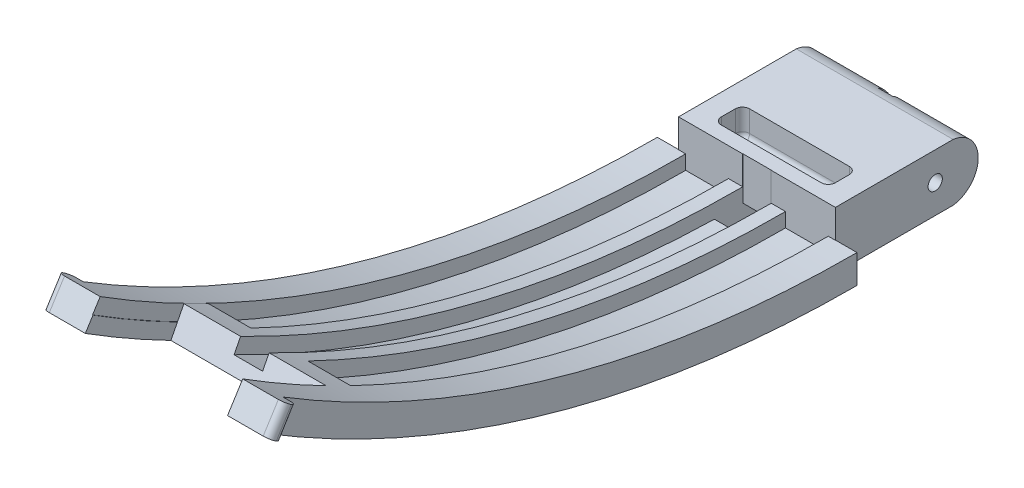
SolidWorks part; units mm, degrees
ref_plane "Alzado" through (0, 0, 0) normal (0, 0, 1) x (1, 0, 0)
ref_plane "Planta" through (0, 0, 0) normal (0, 1, 0) x (1, 0, 0)
ref_plane "Vista lateral" through (0, 0, 0) normal (1, 0, 0) x (0, 0, -1)
sketch "Croquis1" plane through (0, 0, 0) normal (0, 1, 0) x (1, 0, 0)
  line L1 (39.1869, -12.1528) -> (50.1869, -12.1528)
  line L2 (39.1869, -12.1528) -> (39.1869, -22.1528)
  line L3 (39.1869, -22.1528) -> (50.1869, -22.1528)
  line L4 (50.1869, -12.1528) -> (50.1869, -22.1528)
  dimension "D1" = 10
  dimension "D2" = 11
extrude "Saliente-Extruir1" add sketch "Croquis1" along normal blind 4
sketch "Croquis2" plane through (39.1869, 0, 0) normal (-1, 0, 0) x (0, 0, 1)
  line L0 (12.1528, 0) -> (12.1528, 2)
  line L1 (12.1528, 4) -> (12.1528, 0) construction
  line L2 (12.1528, 2) -> (22.1528, 2)
  line L3 (22.1528, 4) -> (22.1528, 0) construction
  line L4 (12.1528, 2) -> (19.1486, 2)
  line L5 (22.1528, 2) -> (15.1528, 2)
  line L6 (12.1528, 2) -> (15.1528, 2)
  circle A0 centre (15.1528, 2) radius 0.5
  dimension "D2" = 1
  dimension "D1" = 7
  dimension "D3" = 3
extrude "Cortar-Extruir1" cut sketch "Croquis2" against normal blind 12 contours A0
sketch "Croquis3" plane through (0, 4, 0) normal (0, 1, 0) x (1, 0, 0)
  line L0 (39.1869, -22.1528) -> (50.1869, -22.1528)
  line L1 (39.1869, -22.1528) -> (50.1869, -22.1528) construction
  line L2 (39.1869, -12.1528) -> (39.1869, -22.1528) construction
  line L3 (40.6869, -19.1753) -> (48.6869, -19.1753)
  line L4 (40.6869, -19.1753) -> (40.6869, -21.1528)
  line L5 (40.6869, -21.1528) -> (48.6869, -21.1528)
  line L6 (48.6869, -19.1753) -> (48.6869, -21.1528)
  line L7 (50.1869, -22.1528) -> (50.1869, -12.1528) construction
  dimension "D1" = 1
  dimension "D2" = 1.5
  dimension "D3" = 1.5
extrude "Cortar-Extruir2" cut sketch "Croquis3" against normal blind 2 contours L6 L3 L4 L5 region at (44.6869, 4, 20.1641)
fillet "Redondeo6" radius 0.5 4 edges at (48.6869, 3, 19.1753) (48.6869, 3, 21.1528) (40.6869, 3, 21.1528) (40.6869, 3, 19.1753)
fillet "Redondeo8" radius 0.5 8 edges at (48.5405, 2, 19.3218) (44.6869, 2, 19.1753) (40.8334, 2, 19.3218) (40.6869, 2, 20.1641) (40.8334, 2, 21.0064) (44.6869, 2, 21.1528) (48.5405, 2, 21.0064) (48.6869, 2, 20.1641)
sketch "Croquis4" plane through (50.1869, 0, 0) normal (1, 0, 0) x (0, 0, -1)
  line L0 (-22.1528, 4) -> (-22.1528, 0)
  line L1 (-12.1528, 2) -> (-14.1528, 2)
  line L2 (-12.1528, 4) -> (-12.1528, 0) construction
  line L3 (-12.1528, 2) -> (-12.1528, 4)
  line L4 (-12.1528, 0) -> (-12.1528, 2)
  line L5 (-12.1528, 4) -> (-14.1528, 4.0162)
  circle A0 centre (-14.1528, 2) radius 2.0162
  spline S0 degree 1 poles (-14.1528, -0.0162) (-12.1528, 0) knots 0 0 1 1
  line M2 (-22.1528, 0) -> (-12.1528, 0)
  line M3 (-12.1528, 0) -> (-12.1528, 4)
  line M4 (-12.1528, 4) -> (-22.1528, 4)
  dimension "D1" = 2
extrude "Cortar-Extruir3" cut sketch "Croquis4" against normal blind 20 contours A0 L3 M4 | A0 M2 M3 region at (50.1869, 3.5672, 12.5857) region at (50.1869, 0.4328, 12.5857)
sketch "Croquis5" plane through (0, 0, 0) normal (0, -1, 0) x (1, 0, 0)
  line L0 (44.6869, 17.97) -> (44.6869, 12.1528)
  line L1 (39.1869, 12.1528) -> (50.1869, 12.1528) construction
  line L2 (44.6869, 12.1528) -> (44.6869, 17.97)
  line L3 (44.6869, 17.97) -> (44.6869, 22.1528)
  line L4 (39.1869, 22.1528) -> (50.1869, 22.1528) construction
  line L5 (44.6869, 22.1528) -> (44.6869, 20.1528)
  line L6 (39.1869, 13.8975) -> (39.1869, 22.1528) construction
  line L7 (44.6869, 20.1528) -> (45.1869, 20.1528)
  line L8 (44.6869, 20.1528) -> (44.6869, 12.1528)
  line L9 (44.6869, 12.1528) -> (45.1869, 12.1528)
  line L10 (45.1869, 20.1528) -> (45.1869, 12.1528)
  line L11 (44.6869, 12.1528) -> (44.1869, 12.1528)
  line L12 (44.6869, 12.1528) -> (44.6869, 20.1528)
  line L13 (44.6869, 20.1528) -> (44.1869, 20.1528)
  line L14 (44.1869, 12.1528) -> (44.1869, 20.1528)
  line L15 (44.6869, 20.1528) -> (43.6869, 20.1528)
  line L16 (44.6869, 20.1528) -> (44.6869, 22.1528)
  line L17 (44.6869, 22.1528) -> (43.6869, 22.1528)
  line L18 (43.6869, 20.1528) -> (43.6869, 22.1528)
  line L19 (44.6869, 20.1528) -> (45.6869, 20.1528)
  line L20 (44.6869, 20.1528) -> (44.6869, 22.1528)
  line L21 (44.6869, 22.1528) -> (45.6869, 22.1528)
  line L22 (45.6869, 20.1528) -> (45.6869, 22.1528)
  line L23 (50.1869, 22.1528) -> (50.1869, 13.8975) construction
  line M1 (39.1869, 13.8975) -> (50.1869, 13.8975)
  dimension "D1" = 2
  dimension "D2" = 0.5
  dimension "D3" = 0.5
  dimension "D4" = 1
  dimension "D5" = 1
  dimension "D6" = 5
  dimension "D7" = 5
extrude "Cortar-Extruir4" cut sketch "Croquis5" against normal blind 1 contours L14 L0 L3 L13 M1 | L10 L7 L3 L0 M1 | L14 L11 L0 M1 | L10 L0 L9 M1 region at (44.9369, 0, 17.0252) region at (44.4369, 0, 17.0252) region at (44.9369, 0, 13.0252) region at (44.4369, 0, 13.0252)
sketch "Croquis6" plane through (0, 0, 22.1528) normal (0, 0, 1) x (1, 0, 0)
  line L0 (45.1869, 0) -> (45.1869, 4)
  line L1 (39.1869, 4) -> (50.1869, 4) construction
  line L2 (45.1869, 4) -> (43.9494, 4)
  line L3 (43.9494, 4) -> (44.1869, 0)
sketch "Croquis7" plane through (0, 1, 0) normal (0, -1, 0) x (1, 0, 0)
  line L1 (39.1869, 12.1528) -> (50.1869, 12.1528) construction
  line L2 (45.1869, 12.4021) -> (44.1869, 12.4021)
  line L3 (45.1869, 12.4021) -> (45.1869, 12.1528)
  line L4 (45.1869, 12.1528) -> (44.1869, 12.1528)
  line L5 (44.1869, 12.4021) -> (44.1869, 12.1528)
  line L6 (45.1869, 13.8975) -> (45.1869, 12.4021) construction
  line L7 (44.1869, 12.4021) -> (45.1869, 12.4021)
  line L8 (44.1869, 12.4021) -> (44.1869, 13.1498)
  line L9 (44.1869, 13.1498) -> (45.1869, 13.1498)
  line L10 (45.1869, 12.4021) -> (45.1869, 13.1498)
  line M1 (45.1869, 12.4021) -> (45.1869, 20.1528)
  line M3 (44.1869, 20.1528) -> (44.1869, 12.4021)
  line M4 (44.1869, 12.4021) -> (45.1869, 12.4021)
  dimension "D1" = 0.2492
  dimension "D2" = 1
  dimension "D3" = 0.7477
extrude "Cortar-Extruir6" cut sketch "Croquis7" against normal blind 5 and the other way blind 12 contours L9 M3 M4 M1 | L5 L4 L3 M4 region at (44.6869, 1, 12.2774) region at (44.6869, 1, 12.7759)
ref_plane "Plano1" through (44.1869, 1, 13.1498) normal (0, 0, 1) x (1, 0, 0)
sketch "Croquis9" plane through (0, 0, 0) normal (0, -1, 0) x (1, 0, 0)
  line L1 (43.6869, 22.1528) -> (45.6869, 22.1528)
  line L2 (45.6869, 20.1528) -> (43.6869, 20.1528)
  line L3 (39.1869, 13.8975) -> (39.1869, 22.1528) construction
  line L4 (45.6869, 20.1528) -> (45.6869, 22.1528)
  line L5 (45.1869, 22.1528) -> (43.9494, 22.1528) construction
  line L6 (39.1869, 22.1528) -> (50.1869, 22.1528) construction
  line L11 (43.6869, 20.1528) -> (43.6869, 22.1528)
  dimension "D1" = 4.5
extrude "Cortar-Extruir7" cut sketch "Croquis9" against normal blind 1
fillet "Redondeo10" radius 0.25 2 edges at (45.6869, 0.5, 20.1528) (43.6869, 0.5, 20.1528)
sketch "Croquis11" plane through (0, 0, 22.1528) normal (0, 0, 1) x (1, 0, 0)
  line L0 (43.6869, 0) -> (45.6869, 0)
  line L1 (50.1869, 4) -> (50.1869, 0) construction
  line L2 (43.6869, 0) -> (37.6869, 0)
  line L3 (45.6869, 0) -> (51.6869, 0)
  line L4 (44.6869, 0) -> (44.6869, 79)
  line L5 (37.6869, 0) -> (51.6869, 0)
  line L6 (37.6869, 0) -> (37.6869, 2)
  line L7 (37.6869, 2) -> (51.6869, 2)
  line L8 (51.6869, 0) -> (51.6869, 2)
  line L9 (37.6869, 0) -> (50.1869, 0)
  line L10 (37.6869, 0) -> (37.6869, 1)
  line L11 (50.1869, 0) -> (50.1869, 1)
  line L13 (37.6869, 1) -> (50.1869, 1)
  line L14 (50.1869, 0) -> (50.1869, 1)
  line L15 (37.6869, 2) -> (39.6869, 2)
  line L16 (37.6869, 2) -> (37.6869, 1)
  line L17 (50.1869, 2) -> (50.1869, 1)
  line L18 (37.6869, 1) -> (39.6869, 1)
  line L19 (39.6869, 2) -> (39.6869, 1)
  line L20 (51.6869, 2) -> (49.6869, 2)
  line L21 (51.6869, 2) -> (51.6869, 1)
  line L22 (51.6869, 1) -> (49.6869, 1)
  line L23 (49.6869, 2) -> (49.6869, 1)
  line L24 (39.6869, 1) -> (42.6869, 1)
  line L25 (39.6869, 1) -> (39.6869, 2)
  line L26 (39.6869, 2) -> (42.6869, 2)
  line L27 (42.6869, 1) -> (42.6869, 2)
  line L28 (49.6869, 1) -> (46.6869, 1)
  line L29 (49.6869, 1) -> (49.6869, 2)
  line L30 (49.6869, 2) -> (46.6869, 2)
  line L31 (46.6869, 1) -> (46.6869, 2)
  line L32 (42.6869, 2) -> (43.6869, 2)
  line L33 (42.6869, 2) -> (42.6869, 1)
  line L34 (42.6869, 1) -> (43.6869, 1)
  line L35 (43.6869, 2) -> (43.6869, 1)
  line L36 (46.6869, 1) -> (45.6869, 1)
  line L37 (46.6869, 1) -> (46.6869, 2)
  line L38 (46.6869, 2) -> (45.6869, 2)
  line L39 (45.6869, 1) -> (45.6869, 2)
  line L40 (44.6869, 79) -> (52.6633, 79)
  dimension "D1" = 6
  dimension "D2" = 6
  dimension "D3" = 2
  dimension "D4" = 2
  dimension "D5" = 2
  dimension "D6" = 3
  dimension "D7" = 3
  dimension "D8" = 1
  dimension "D9" = 1
  dimension "D10" = 2
  dimension "D11" = 79
revolve "Revolución5" add sketch "Croquis11" angle 32.23 about L40 region at (44.1869, 0.5, 22.1528) region at (41.4369, 0.5, 22.1528) region at (45.1869, 0.5, 22.1528) region at (38.4369, 0.5, 22.1528) region at (43.1869, 1.5, 22.1528) region at (47.9369, 0.5, 22.1528) region at (39.4369, 1.5, 22.1528) region at (38.4369, 1.5, 22.1528) region at (50.9369, 0.5, 22.1528) region at (46.1869, 1.5, 22.1528) region at (49.9369, 1.5, 22.1528) region at (50.9369, 1.5, 22.1528) other way angle 0.01 reverse direction yes
sketch "Croquis13" plane through (0, 1, 0) normal (0, -1, 0) x (-1, 0, 0)
  line L1 (-43.6869, -22.139) -> (-45.6869, -22.139)
  line L2 (-43.6869, -22.139) -> (-43.6869, -24.139)
  line L3 (-43.6869, -24.139) -> (-45.6869, -24.139)
  line L4 (-45.6869, -22.139) -> (-45.6869, -24.139)
  dimension "D1" = 2
extrude "Cortar-Extruir13" cut sketch "Croquis13" along normal blind 7 and the other way blind 10
sketch "Croquis14" plane through (0, 32.464, 51.4921) normal (0, 0.5333, 0.8459) x (1, 0, 0)
  line L0 (37.6869, -23.9873) -> (51.6869, -23.9873) construction
  line L1 (39.7134, -23.9873) -> (49.6869, -23.9873)
  line L2 (39.7134, -23.9873) -> (39.7134, -21.9873)
  line L3 (39.7134, -21.9873) -> (49.6869, -21.9873)
  line L4 (49.6869, -23.9873) -> (49.6869, -21.9873)
  line L5 (44.7002, -23.9873) -> (44.7002, 55.0127)
  line L6 (44.7002, 55.0127) -> (69.4578, 55.0127)
  dimension "D1" = 79
revolve "Cortar-Revolución1" cut sketch "Croquis14" angle 5.013 about L6 region at (42.3705, 12.737, 63.9293) region at (47.0254, 12.737, 63.9293)
sketch "Croquis15" plane through (0, 32.464, 51.4921) normal (0, 0.5333, 0.8459) x (1, 0, 0)
  line L1 (37.6869, -21.9873) -> (36.6869, -21.9873)
  line L2 (37.6869, -21.9873) -> (37.6869, -23.9873)
  line L3 (37.6869, -23.9873) -> (36.6869, -23.9873)
  line L4 (36.6869, -21.9873) -> (36.6869, -23.9873)
  line L5 (51.6869, -23.9873) -> (52.6869, -23.9873)
  line L6 (51.6869, -23.9873) -> (51.6869, -21.9873)
  line L7 (51.6869, -21.9873) -> (52.6869, -21.9873)
  line L8 (52.6869, -23.9873) -> (52.6869, -21.9873)
  line L9 (39.7134, -23.9873) -> (39.7134, 55.0127)
  line L10 (39.7134, 55.0127) -> (49.8688, 55.0127)
  dimension "D1" = 1
  dimension "D2" = 1
  dimension "D3" = 79
revolve "Revolución6" add sketch "Croquis15" angle 0.716 about L10 region at (37.1869, 13.0187, 63.7517) region at (52.1869, 13.0187, 63.7517)
fillet "Redondeo11" radius 0.5 4 edges at (52.6869, 12.5039, 62.9237) (52.6869, 13.0187, 63.7517) (36.6869, 12.5039, 62.9237) (36.6869, 13.0187, 63.7517)
sketch "Croquis16" plane through (0, 25.5348, 49.6498) normal (0, 0.4574, 0.8893) x (1, 0, 0)
  line L0 (44.7002, -18.8783) -> (44.7002, 60.1217)
  line L1 (39.7134, -18.8783) -> (49.6869, -18.8783)
  line L2 (39.7134, -18.8783) -> (39.7134, -16.8783)
  line L3 (39.7134, -16.8783) -> (49.6869, -16.8783)
  line L4 (49.6869, -18.8783) -> (49.6869, -16.8783)
  line L6 (44.7002, 60.1217) -> (46.7199, 60.1217)
  dimension "D1" = 79
revolve "Revolución7" add sketch "Croquis16" angle 1.432 about L6 region at (41.2002, 10.0805, 57.5979) region at (48.1869, 10.0805, 57.5979)
